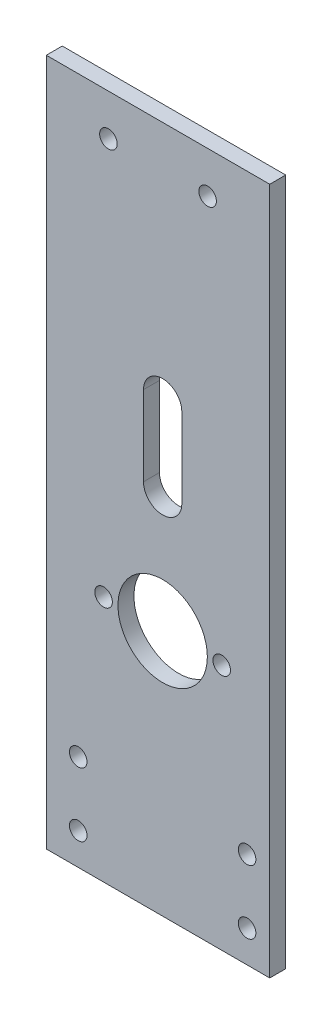
SolidWorks part; units mm, degrees
ref_plane "Front Plane" through (0, 0, 0) normal (0, 0, 1) x (1, 0, 0)
ref_plane "Top Plane" through (0, 0, 0) normal (0, 1, 0) x (1, 0, 0)
ref_plane "Right Plane" through (0, 0, 0) normal (1, 0, 0) x (0, 0, -1)
sketch "Sketch1" plane through (0, 0, 0) normal (0, 0, 1) x (1, 0, 0)
  line L0 (-26.4505, -10) -> (26.4505, 10) construction
  line L2 (-36.4505, -77.3566) -> (-36.4505, 77.3566)
  line L3 (-36.4505, 77.3566) -> (33.5495, 77.3566)
  line L4 (33.5495, -77.3566) -> (33.5495, 77.3566)
  line L5 (-26.4505, 10) -> (26.4505, -10) construction
  line L6 (-36.4505, -77.3566) -> (33.5495, -77.3566)
  line L7 (-18.5, 57.3566) -> (18.5, 57.3566) construction
  line L8 (-15.5, -33.6434) -> (-15.5, -40.6434) construction
  line L9 (-15.5, -68.1434) -> (15.5, -68.1434) construction
  line L11 (-15.5, -68.1434) -> (-15.5, -37.1434) construction
  line L14 (-15.5, -37.1434) -> (15.5, -37.1434) construction
  line L15 (15.5, -68.1434) -> (15.5, -37.1434) construction
  line L16 (-15.5, -68.1434) -> (15.5, -37.1434) construction
  line L17 (-15.5, -37.1434) -> (15.5, -68.1434) construction
  line L18 (-13.95, -33.6434) -> (-13.95, -40.6434)
  line L19 (-17.05, -33.6434) -> (-17.05, -40.6434)
  line L20 (15.5, -33.6434) -> (15.5, -40.6434) construction
  line L21 (17.05, -33.6434) -> (17.05, -40.6434)
  line L22 (13.95, -33.6434) -> (13.95, -40.6434)
  line L23 (15.5, -64.6434) -> (15.5, -71.6434) construction
  line L24 (17.05, -64.6434) -> (17.05, -71.6434)
  line L25 (13.95, -64.6434) -> (13.95, -71.6434)
  line L26 (-15.5, -64.6434) -> (-15.5, -71.6434) construction
  line L27 (-13.95, -64.6434) -> (-13.95, -71.6434)
  line L28 (-17.05, -64.6434) -> (-17.05, -71.6434)
  line L29 (0, -56.1434) -> (0, -49.1434) construction
  line L30 (-12, -56.1434) -> (-12, -49.1434)
  line L31 (12, -56.1434) -> (12, -49.1434)
  line L33 (-36.4505, 77.3566) -> (33.5495, 77.3566)
  line L34 (-36.4505, 77.3566) -> (-36.4505, 195.3566)
  line L35 (-36.4505, 195.3566) -> (33.5495, 195.3566)
  line L36 (33.5495, 77.3566) -> (33.5495, 195.3566)
  line L38 (0, 119.8566) -> (0, 94.8566) construction
  line L39 (6, 119.8566) -> (6, 94.8566)
  line L40 (-6, 119.8566) -> (-6, 94.8566)
  circle A0 centre (-18.5, 57.3566) radius 2.75
  circle A1 centre (18.5, 57.3566) radius 2.75
  circle A2 centre (0, 57.3566) radius 5
  circle A3 centre (-26.4505, 10) radius 2.75
  circle A4 centre (26.4505, 10) radius 2.75
  circle A5 centre (26.4505, -10) radius 2.75
  circle A6 centre (-26.4505, -10) radius 2.75
  circle A7 centre (0, 57.3566) radius 14
  arc A13 (-13.95, -33.6434) -> (-17.05, -33.6434) centre (-15.5, -33.6434) ccw
  arc A14 (-17.05, -40.6434) -> (-13.95, -40.6434) centre (-15.5, -40.6434) ccw
  arc A15 (17.05, -33.6434) -> (13.95, -33.6434) centre (15.5, -33.6434) ccw
  arc A16 (13.95, -40.6434) -> (17.05, -40.6434) centre (15.5, -40.6434) ccw
  arc A17 (17.05, -64.6434) -> (13.95, -64.6434) centre (15.5, -64.6434) ccw
  arc A18 (13.95, -71.6434) -> (17.05, -71.6434) centre (15.5, -71.6434) ccw
  arc A19 (-13.95, -64.6434) -> (-17.05, -64.6434) centre (-15.5, -64.6434) ccw
  arc A20 (-17.05, -71.6434) -> (-13.95, -71.6434) centre (-15.5, -71.6434) ccw
  arc A21 (-12, -56.1434) -> (12, -56.1434) centre (0, -56.1434) ccw
  arc A22 (12, -49.1434) -> (-12, -49.1434) centre (0, -49.1434) ccw
  arc A23 (6, 119.8566) -> (-6, 119.8566) centre (0, 119.8566) ccw
  arc A24 (-6, 94.8566) -> (6, 94.8566) centre (0, 94.8566) ccw
  circle A25 centre (-16.9918, 182.3877) radius 2.75
  circle A26 centre (14.0909, 182.3877) radius 2.75
  point P0 (0, 0)
  point P5 (-36.4505, 0)
  point P6 (0, -52.6434)
  point P25 (-15.5, -37.1434)
  point P38 (15.5, -37.1434)
  point P45 (15.5, -68.1434)
  point P52 (-15.5, -68.1434)
  point P57 (0, -52.6434)
  point P64 (0, 107.3566)
  point P67 (0, 107.3566)
  dimension "D4" = 5.5
  dimension "D5" = 10
  dimension "D6" = 5.5
  dimension "D11" = 28
  dimension "D7" = 12
  dimension "D12" = 1.55
  dimension "D17" = 6
  dimension "D20" = 5.5
  dimension "D1" = 70
  dimension "D2" = 31
  dimension "D3" = 37
  dimension "D8" = 20
  dimension "D9" = 7
  dimension "D10" = 20
  dimension "D13" = 110
  dimension "D14" = 7
  dimension "D15" = 50
  dimension "D16" = 138
  dimension "D18" = 25
  dimension "D19" = 12.9688
  dimension "D21" = 31.0827
extrude "Boss-Extrude1" add sketch "Sketch1" along normal blind 5 contours L2 L6 L4 L3 A7 A6 A5 A4 A3 A1 A0 region at (-1.6829, 0.0831, 0)
extrude "Boss-Extrude2" add sketch "Sketch1<4>" along normal blind 5 contours L3 L36 L35 L34 A24 L40 A23 L39 region at (-1.5273, 137.6121, 0)
sketch "Sketch1<4>" plane through (0, 0, 0) normal (0, 0, 1) x (1, 0, 0) same geometry as "Sketch1"
sketch "Sketch2" plane through (0, 0, 5) normal (0, 0, 1) x (1, 0, 0)
  line L0 (-36.4505, -20) -> (33.5495, -20)
  line L4 (-36.4505, 195.3566) -> (-36.4505, -77.3566)
  line L5 (-36.4505, -77.3566) -> (33.5495, -77.3566)
  line L6 (33.5495, -77.3566) -> (33.5495, 195.3566)
  line L7 (33.5495, 195.3566) -> (-36.4505, 195.3566)
  line L8 (-36.4505, 195.3566) -> (-36.4505, -77.3566)
  line L9 (-36.4505, -77.3566) -> (33.5495, -77.3566)
  line L10 (33.5495, -77.3566) -> (33.5495, 195.3566)
  line L11 (33.5495, 195.3566) -> (-36.4505, 195.3566)
  circle A0 centre (26.4505, -10) radius 2.75 construction
  circle A1 centre (26.4505, -10) radius 2.75
  arc M6 (-12, -49.1434) -> (12, -49.1434) centre (0, -49.1434) cw
  line M7 (12, -49.1434) -> (12, -56.1434)
  arc M8 (12, -56.1434) -> (-12, -56.1434) centre (0, -56.1434) cw
  line M9 (-12, -56.1434) -> (-12, -49.1434)
  arc M10 (-13.95, -71.6434) -> (-17.05, -71.6434) centre (-15.5, -71.6434) cw
  line M11 (-17.05, -71.6434) -> (-17.05, -64.6434)
  arc M12 (-17.05, -64.6434) -> (-13.95, -64.6434) centre (-15.5, -64.6434) cw
  line M13 (-13.95, -64.6434) -> (-13.95, -71.6434)
  arc M14 (17.05, -71.6434) -> (13.95, -71.6434) centre (15.5, -71.6434) cw
  line M15 (13.95, -71.6434) -> (13.95, -64.6434)
  arc M16 (13.95, -64.6434) -> (17.05, -64.6434) centre (15.5, -64.6434) cw
  line M17 (17.05, -64.6434) -> (17.05, -71.6434)
  arc M18 (17.05, -40.6434) -> (13.95, -40.6434) centre (15.5, -40.6434) cw
  line M19 (13.95, -40.6434) -> (13.95, -33.6434)
  arc M20 (13.95, -33.6434) -> (17.05, -33.6434) centre (15.5, -33.6434) cw
  line M21 (17.05, -33.6434) -> (17.05, -40.6434)
  arc M22 (-13.95, -40.6434) -> (-17.05, -40.6434) centre (-15.5, -40.6434) cw
  line M23 (-17.05, -40.6434) -> (-17.05, -33.6434)
  arc M24 (-17.05, -33.6434) -> (-13.95, -33.6434) centre (-15.5, -33.6434) cw
  line M25 (-13.95, -33.6434) -> (-13.95, -40.6434)
  line M33 (-36.4505, 195.3566) -> (-36.4505, -77.3566)
  line M34 (-36.4505, -77.3566) -> (33.5495, -77.3566)
  line M35 (33.5495, -77.3566) -> (33.5495, 195.3566)
  dimension "D2" = 10
  dimension "D1" = 0
extrude "Cut-Extrude1" cut sketch "Sketch2" against normal blind 10 contours L0 M33 M34 M35 M25 M22 M23 M24 M21 M18 M19 M20 M17 M14 M15 M16 M13 M10 M11 M12 M9 M6 M7 M8 region at (-1.4505, -20.905, 5)
